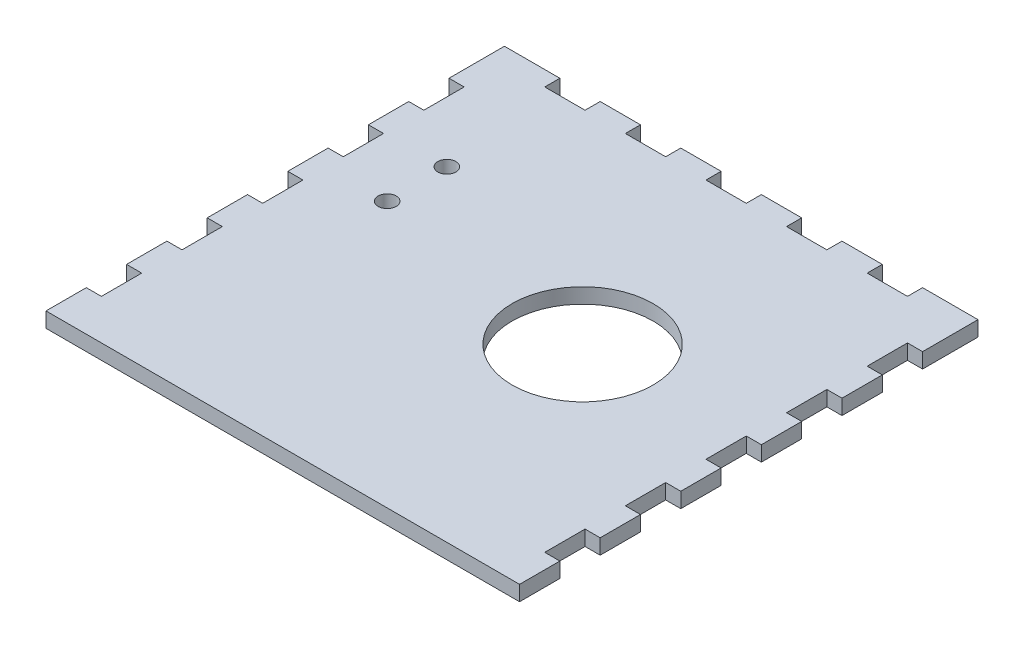
SolidWorks part; units mm, degrees
ref_plane "Front Plane" through (0, 0, 0) normal (0, 0, 1) x (1, 0, 0)
ref_plane "Top Plane" through (0, 0, 0) normal (0, 1, 0) x (1, 0, 0)
ref_plane "Right Plane" through (0, 0, 0) normal (1, 0, 0) x (0, 0, -1)
sketch "Sketch1" plane through (0, 0, 0) normal (0, 1, 0) x (1, 0, 0)
  line L1 (-139.7, -139.7) -> (139.7, -139.7)
  line L2 (-139.7, -139.7) -> (-139.7, 139.7)
  line L3 (-139.7, 139.7) -> (139.7, 139.7)
  line L4 (139.7, -139.7) -> (139.7, 139.7)
  line L5 (-139.7, -139.7) -> (139.7, 139.7) construction
  line L6 (-139.7, 139.7) -> (139.7, -139.7) construction
  point P0 (0, 0)
  dimension "D1" = 279.4
  dimension "D2" = 279.4
extrude "Boss-Extrude1" add sketch "Sketch1" along normal blind 9.525
sketch "Sketch2" plane through (139.7, 0, 0) normal (1, 0, 0) x (0, 0, -1)
  line L0 (-139.7, 9.525) -> (139.7, 9.525) construction
  line L1 (-139.7, 0) -> (-114.3, 0)
  line L2 (-139.7, 0) -> (-139.7, 9.525)
  line L3 (-139.7, 9.525) -> (-114.3, 9.525)
  line L4 (-114.3, 0) -> (-114.3, 9.525)
  dimension "D1" = 25.4
extrude "Boss-Extrude2" add sketch "Sketch2" along normal blind 9.525
pattern_linear "LPattern1" count 6 spacing 50.8 along (0, 0, -1) of "Boss-Extrude2"
mirror "Mirror1" about plane through (0, 0, 0) normal (1, 0, 0) of "LPattern1"
sketch "Sketch3" plane through (0, 0, -139.7) normal (0, 0, -1) x (-1, 0, 0)
  line L0 (-149.225, 9.525) -> (149.225, 9.525) construction
  line L1 (-139.7, 9.525) -> (-114.3, 9.525)
  line L2 (-139.7, 9.525) -> (-139.7, 0)
  line L3 (-139.7, 0) -> (-114.3, 0)
  line L4 (-114.3, 9.525) -> (-114.3, 0)
  line L5 (-149.225, 0) -> (149.225, 0) construction
  line L6 (-149.225, 0) -> (-149.225, 9.525) construction
  dimension "D1" = 9.525
  dimension "D2" = 25.4
extrude "Boss-Extrude3" add sketch "Sketch3" along normal blind 9.525
pattern_linear "LPattern2" count 6 spacing 50.8 along (-1, 0, 0) of "Boss-Extrude3"
sketch "Sketch5" plane through (0, 0, -139.7) normal (0, 0, -1) x (-1, 0, 0)
  line L0 (158.9088, 0) -> (-158.9088, 0) construction
  line L1 (-149.225, 9.525) -> (-139.7, 9.525)
  line L2 (-149.225, 9.525) -> (-149.225, 0)
  line L3 (-149.225, 0) -> (-139.7, 0)
  line L4 (-139.7, 9.525) -> (-139.7, 0)
  line L5 (-139.7, 9.525) -> (-139.7, 0) construction
extrude "Boss-Extrude4" add sketch "Sketch5" along normal blind 9.525
mirror "Mirror2" about plane through (0, 0, 0) normal (1, 0, 0) of "Boss-Extrude4"
sketch "Sketch6" plane through (0, 9.525, 0) normal (0, 1, 0) x (1, 0, 0)
  line L0 (63.5, 139.7) -> (38.1, 139.7) construction
  line L1 (139.7, -12.7) -> (139.7, 12.7) construction
  circle A0 centre (38.1, 11.176) radius 44.45
  dimension "D1" = 128.524
  dimension "D2" = 101.6
extrude "Cut-Extrude1" cut sketch "Sketch6" against normal through all
sketch "Sketch7" plane through (0, 9.525, 0) normal (0, 1, 0) x (1, 0, 0)
  line L0 (-139.7, 63.5) -> (-139.7, 38.1) construction
  line L1 (-139.7, 114.3) -> (-139.7, 88.9) construction
  line L2 (-88.9, 139.7) -> (-114.3, 139.7) construction
  circle A0 centre (-101.6, 65.278) radius 5.715
  circle A1 centre (-101.6, 27.686) radius 5.715
  dimension "D1" = 11.43
  dimension "D2" = 11.43
  dimension "D3" = 38.1
  dimension "D4" = 38.1
  dimension "D5" = 37.592
  dimension "D6" = 74.422
extrude "Cut-Extrude2" cut sketch "Sketch7" against normal through all
sketch "Sketch9" plane through (0, 9.525, 0) normal (0, 1, 0) x (1, 0, 0)
  circle A0 centre (-101.6, 65.2827) radius 11 construction
  circle A1 centre (-101.6, 27.6073) radius 25.4
  circle A2 centre (-101.6, 27.6073) radius 25.4
  circle A3 centre (-101.6, 65.2827) radius 11
  dimension "D1" = 0
